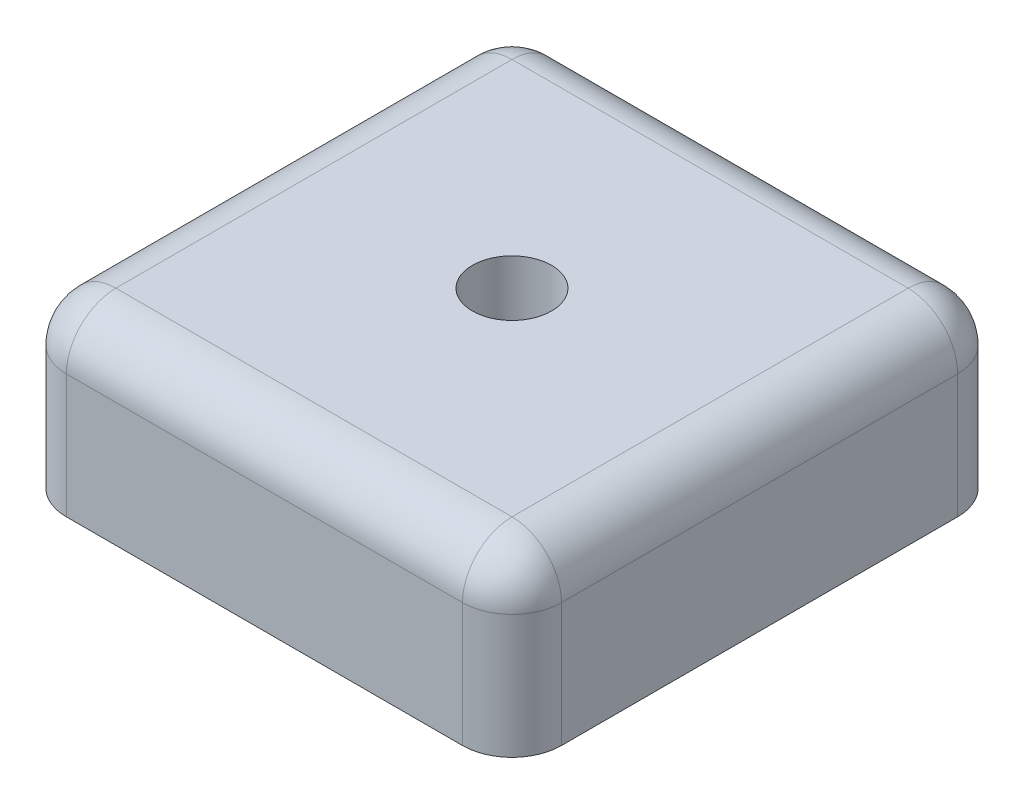
SolidWorks part; units mm, degrees
ref_plane "Front Plane" through (0, 0, 0) normal (0, 0, 1) x (1, 0, 0)
ref_plane "Top Plane" through (0, 0, 0) normal (0, 1, 0) x (1, 0, 0)
ref_plane "Right Plane" through (0, 0, 0) normal (1, 0, 0) x (0, 0, -1)
sketch "Sketch2" plane through (0, 0, 0) normal (0, 1, 0) x (1, 0, 0)
  line L0 (0, 20) -> (20, 20)
  line L1 (0, 0) -> (20, 0)
  line L2 (0, 0) -> (0, 20)
  line L4 (20, 0) -> (20, 20)
  dimension "D1" = 20
  dimension "D3" = 20
extrude "Boss-Extrude1" add sketch "Sketch2" along normal blind 7 contours L4 L0 L2 L1
sketch "Sketch3" plane through (0, 7, 0) normal (0, 1, 0) x (1, 0, 0)
  line L0 (0, 0) -> (20, 20) construction
  circle A0 centre (10, 10) radius 1.6
  dimension "D1" = 3.2
extrude "Cut-Extrude1" cut sketch "Sketch3" against normal through all
fillet "Fillet1" radius 2 8 edges at (0, 3.5, -20) (20, 3.5, -20) (20, 3.5, 0) (0, 3.5, 0) (10, 7, 0) (20, 7, -10) (10, 7, -20) (0, 7, -10)
